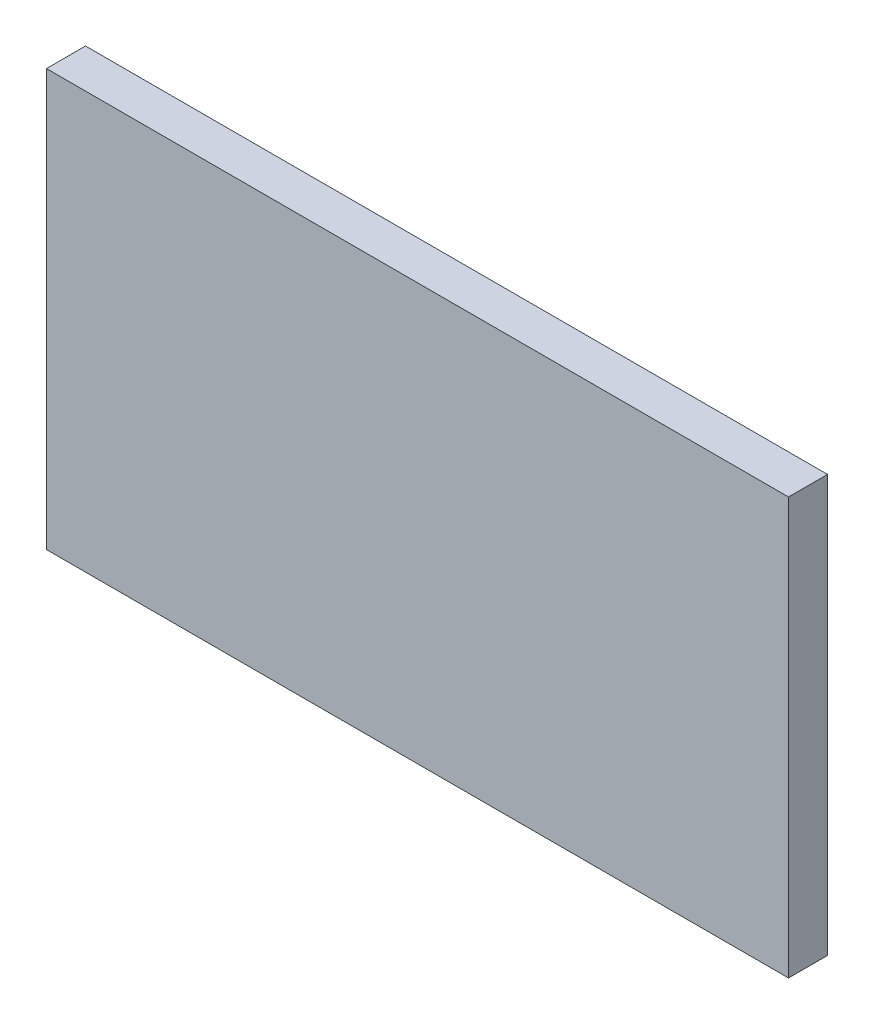
SolidWorks part; units mm, degrees
material "Oak"
ref_plane "Front Plane" through (0, 0, 0) normal (0, 0, 1) x (1, 0, 0)
ref_plane "Top Plane" through (0, 0, 0) normal (0, 1, 0) x (1, 0, 0)
ref_plane "Right Plane" through (0, 0, 0) normal (1, 0, 0) x (0, 0, -1)
sketch "Sketch1" plane through (0, 0, 0) normal (0, 0, 1) x (1, 0, 0)
  line L1 (-36.0143, 24.5902) -> (20.9857, 24.5902)
  line L2 (-36.0143, 24.5902) -> (-36.0143, -7.4098)
  line L3 (-36.0143, -7.4098) -> (20.9857, -7.4098)
  line L4 (20.9857, 24.5902) -> (20.9857, -7.4098)
  dimension "D1" = 32
  dimension "D2" = 57
extrude "Boss-Extrude1" add sketch "Sketch1" along normal blind 3
